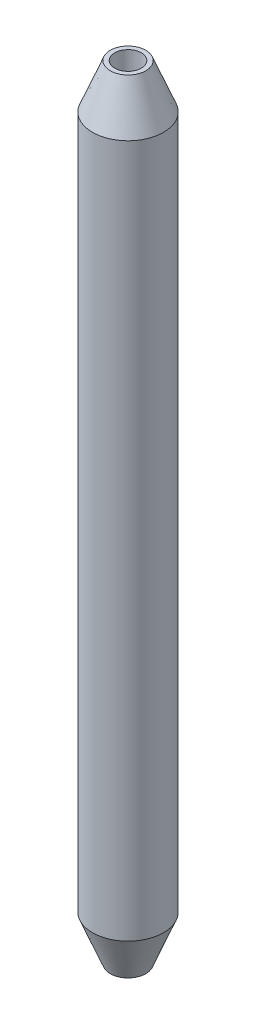
SolidWorks part; units mm, degrees
material "AISI 1045 Steel, cold drawn"
ref_plane "Front Plane" through (0, 0, 0) normal (1, 0, 0) x (0, 1, 0)
ref_plane "Top Plane" through (0, 0, 0) normal (0, 0, 1) x (0, 1, 0)
ref_plane "Right Plane" through (0, 0, 0) normal (0, 1, 0) x (-1, 0, 0)
sketch "Sketch2" plane through (0, 0, 0) normal (1, 0, 0) x (0, 1, 0)
  line L0 (0, 28.3342) -> (0, -17.928) construction
  line L1 (-38.9544, 0) -> (64.0893, 0) construction
  line L2 (-39, 4) -> (39, 4)
  line L3 (39, 4) -> (44, 2)
  line L4 (44, 2) -> (44, 1.5)
  line L5 (44, 1.5) -> (-44, 1.5)
  line L6 (-44, 2) -> (-44, 1.5)
  line L7 (-39, 4) -> (-44, 2)
  dimension "D1" = 88
  dimension "D2" = 8
  dimension "D3" = 5
  dimension "D4" = 4
  dimension "D5" = 3
revolve "Revolve1" add sketch "Sketch2" angle 360 about L1
ref_axis "Axis1" through (0, 33.1326, 0) along (0, -1, 0)
